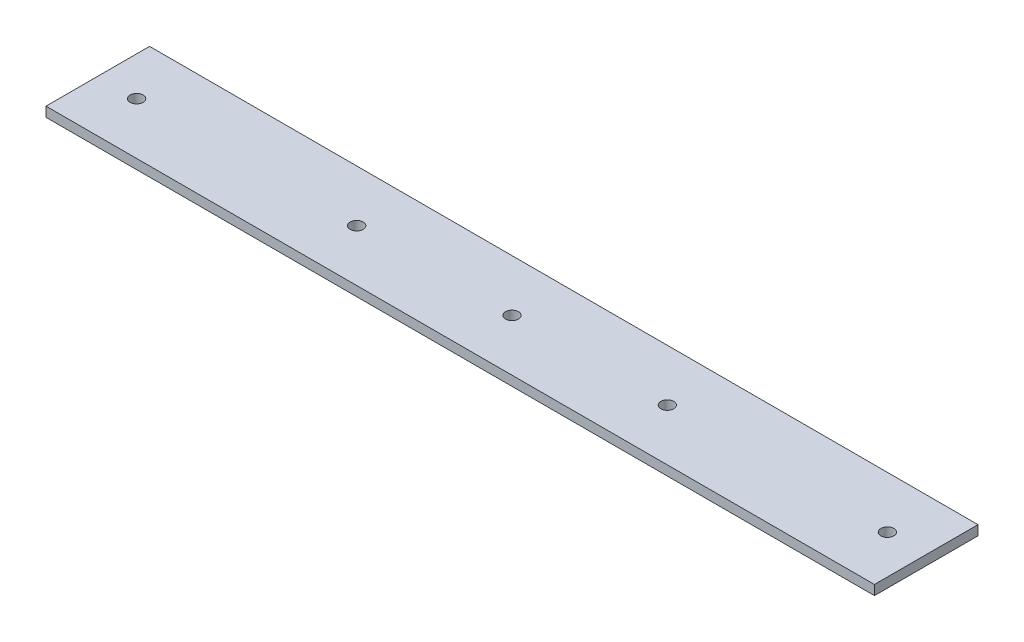
SolidWorks part; units mm, degrees
ref_plane "Front Plane" through (0, 0, 0) normal (0, 0, 1) x (1, 0, 0)
ref_plane "Top Plane" through (0, 0, 0) normal (0, 1, 0) x (1, 0, 0)
ref_plane "Right Plane" through (0, 0, 0) normal (1, 0, 0) x (0, 0, -1)
sketch "Sketch1" plane through (0, 0, 0) normal (0, 1, 0) x (1, 0, 0)
  line L1 (0, 0) -> (406.4, 0)
  line L2 (0, 0) -> (0, 50.8)
  line L3 (0, 50.8) -> (406.4, 50.8)
  line L4 (406.4, 0) -> (406.4, 50.8)
  dimension "D1" = 406.4
  dimension "D2" = 50.8
extrude "Boss-Extrude1" add sketch "Sketch1" along normal blind 4.7625
sketch "Sketch2" plane through (0, 4.7625, 0) normal (0, 1, 0) x (1, 0, 0)
  line L0 (0, 0) -> (406.4, 0) construction
  line L1 (0, 50.8) -> (0, 0) construction
  circle A0 centre (19.05, 25.4) radius 3.175
  circle A1 centre (387.35, 25.4) radius 3.175
  dimension "D1" = 25.4
  dimension "D2" = 25.4
  dimension "D3" = 19.05
  dimension "D4" = 387.35
extrude "Cut-Extrude1" cut sketch "Sketch2" against normal blind 244.602
sketch "Sketch3" plane through (0, 4.7625, 0) normal (0, 1, 0) x (1, 0, 0)
  line L0 (406.4, 50.8) -> (0, 50.8) construction
  line L1 (406.4, 0) -> (406.4, 50.8) construction
  circle A0 centre (279.4, 25.4) radius 3.175
  circle A1 centre (203.2, 25.4) radius 3.175
  circle A2 centre (127, 25.4) radius 3.175
  dimension "D1" = 25.4
  dimension "D2" = 25.4
  dimension "D3" = 25.4
  dimension "D4" = 203.2
  dimension "D5" = 279.4
  dimension "D6" = 127
extrude "Cut-Extrude2" cut sketch "Sketch3" against normal blind 244.602
